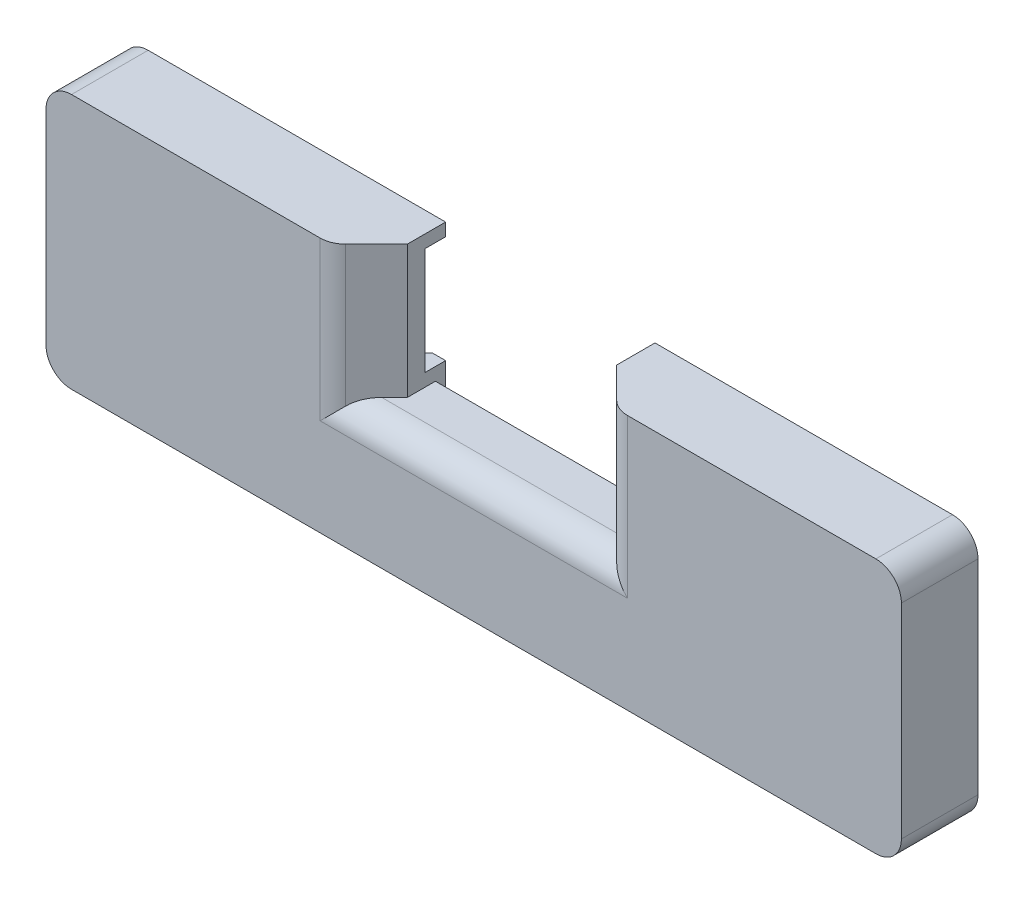
SolidWorks part; units mm, degrees
ref_plane "Front Plane" through (0, 0, 0) normal (0, 0, 1) x (1, 0, 0)
ref_plane "Top Plane" through (0, 0, 0) normal (0, 1, 0) x (1, 0, 0)
ref_plane "Right Plane" through (0, 0, 0) normal (1, 0, 0) x (0, 0, -1)
sketch "Sketch1" plane through (0, 0, 0) normal (0, 0, 1) x (1, 0, 0)
  line L0 (0, 0) -> (0, 24) construction
  line L1 (-167.5, -50) -> (167.5, -50)
  line L2 (-167.5, -50) -> (-167.5, 50)
  line L3 (-167.5, 50) -> (-41, 50)
  line L4 (167.5, -50) -> (167.5, 50)
  line L5 (-167.5, -50) -> (167.5, 50) construction
  line L6 (-167.5, 50) -> (167.5, -50) construction
  line L7 (41, 50) -> (167.5, 50)
  line L8 (-41, -2) -> (41, -2)
  line L9 (-41, -2) -> (-41, 50)
  line L11 (41, -2) -> (41, 50)
  line L12 (-41, -2) -> (41, 50) construction
  line L13 (-41, 50) -> (41, -2) construction
  line L14 (0, 0) -> (-167.5, 0) construction
  line L15 (0, 0) -> (167.5, 1.5601) construction
  point P0 (0, 0)
  point P8 (0, 24)
  dimension "D1" = 335
  dimension "D2" = 100
  dimension "D3" = 82
  dimension "D4" = 52
extrude "Boss-Extrude1" add sketch "Sketch1" against normal blind 5
sketch "Sketch2" plane through (0, 0, -5) normal (0, 0, -1) x (-1, 0, 0)
  line L0 (167.5, -50) -> (-167.5, -50) construction
  line L1 (-167.5, 50) -> (-162.5, 50)
  line L2 (-167.5, 50) -> (-167.5, -50)
  line L3 (-167.5, -50) -> (-162.5, -50)
  line L4 (-162.5, 45) -> (-162.5, -45)
  line L5 (-41, 50) -> (-41, -2) construction
  line L6 (-162.5, 50) -> (-41, 50)
  line L8 (-162.5, 45) -> (-46, 45)
  line L9 (-41, 50) -> (-41, 45)
  line L11 (167.5, 50) -> (162.5, 50)
  line L12 (167.5, 50) -> (167.5, -50)
  line L13 (167.5, -50) -> (162.5, -50)
  line L14 (162.5, 45) -> (162.5, -45)
  line L15 (41, 50) -> (162.5, 50)
  line L16 (41, 50) -> (41, 45)
  line L17 (46, 45) -> (162.5, 45)
  line L19 (-162.5, -50) -> (162.5, -50)
  line L21 (-162.5, -45) -> (162.5, -45)
  line L23 (-41, -2) -> (41, -2)
  line L25 (-41, -7) -> (41, -7)
  line L27 (-41, -7) -> (-46, -7)
  line L28 (-41, -2) -> (-41, 45)
  line L30 (-46, -7) -> (-46, 45)
  line L31 (41, -7) -> (46, -7)
  line L32 (41, -2) -> (41, 45)
  line L34 (46, -7) -> (46, 45)
  dimension "D1" = 5
  dimension "D2" = 5
  dimension "D3" = 5
  dimension "D4" = 5
  dimension "D5" = 5
  dimension "D6" = 5
  dimension "D7" = 5
  dimension "D8" = 5
extrude "Boss-Extrude2" add sketch "Sketch2" along normal blind 25
fillet "Fillet1" radius 10 4 edges at (-167.5, 50, -15) (-167.5, -50, -15) (167.5, -50, -15) (167.5, 50, -15)
chamfer "Chamfer3" distance 25 angle 45 2 edges at (-46, 19, -5) (46, 19, -5)
chamfer "Chamfer4" distance 15 angle 45 2 edges at (41, 24, 0) (-41, 24, 0)
sketch "Sketch3" plane through (-41, 0, 0) normal (1, 0, 0) x (0, 0, -1)
  line L0 (30, 50) -> (30, -2) construction
  line L1 (30, 45) -> (22, 45)
  line L2 (30, 45) -> (30, 3)
  line L3 (30, 3) -> (22, 3)
  line L4 (22, 45) -> (22, 3)
  line L5 (30, 50) -> (15, 50) construction
  line L6 (30, -2) -> (15, -2) construction
  dimension "D1" = 5
  dimension "D2" = 5
  dimension "D3" = 8
extrude "Cut-Extrude1" cut sketch "Sketch3" against normal blind 25
sketch "Sketch4" plane through (41, 0, 0) normal (-1, 0, 0) x (0, 0, 1)
  line L0 (-30, -2) -> (-30, 50) construction
  line L1 (-30, 45) -> (-22, 45)
  line L2 (-30, 45) -> (-30, 3)
  line L3 (-30, 3) -> (-22, 3)
  line L4 (-22, 45) -> (-22, 3)
  line L5 (-30, 50) -> (-15, 50) construction
  line L6 (-30, -2) -> (-15, -2) construction
  point P8 (-22.5, 50)
  dimension "D1" = 5
  dimension "D2" = 5
  dimension "D3" = 8
extrude "Cut-Extrude2" cut sketch "Sketch4" against normal blind 25
fillet "Fillet2" radius 10 3 edges at (0, -2, 0) (56, 24, 0) (-56, 24, 0)
sketch "Sketch5" plane through (0, -2, 0) normal (0, 1, 0) x (1, 0, 0)
  line L0 (41, 30) -> (41, 15) construction
  line L1 (-41, 30) -> (41, 30)
  line L2 (-41, 30) -> (-41, 26)
  line L3 (-41, 26) -> (41, 26)
  line L4 (41, 30) -> (41, 26)
  dimension "D1" = 4
extrude "Cut-Extrude3" cut sketch "Sketch5" against normal blind 10
chamfer "Chamfer5" distance 10 angle 45 4 edges at (-162.5, -45, -17.5) (-162.5, 45, -17.5) (162.5, -45, -17.5) (162.5, 45, -17.5)
chamfer "Chamfer6" distance 10 angle 45 1 edges at (0, -7, -5)
